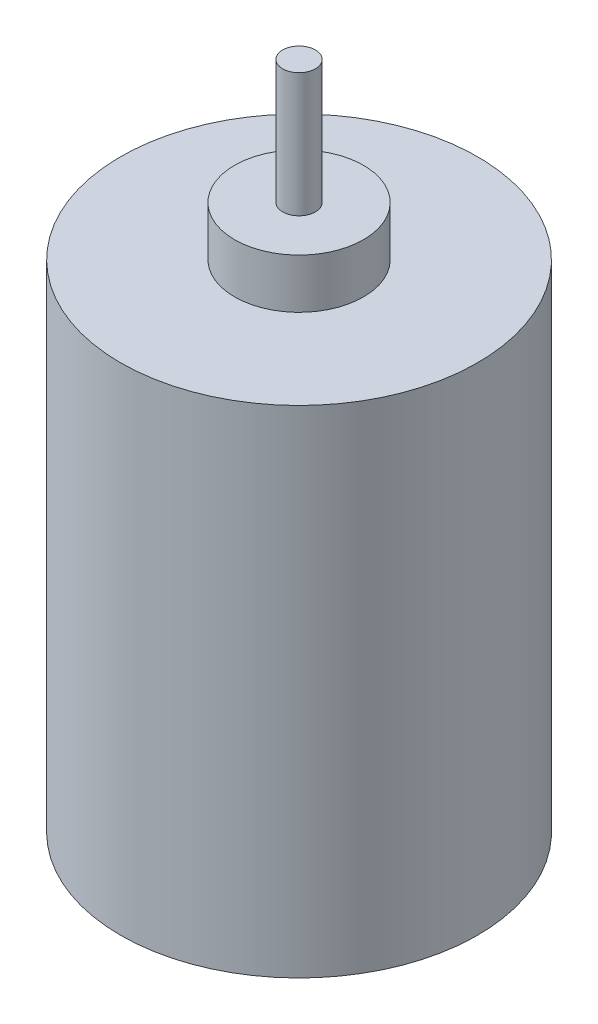
SolidWorks part; units mm, degrees
ref_plane "Front Plane" through (0, 0, 0) normal (0, 0, 1) x (1, 0, 0)
ref_plane "Top Plane" through (0, 0, 0) normal (0, 1, 0) x (1, 0, 0)
ref_plane "Right Plane" through (0, 0, 0) normal (1, 0, 0) x (0, 0, -1)
sketch "Sketch1" plane through (0, 0, 0) normal (0, 1, 0) x (1, 0, 0)
  circle A0 centre (0, 0) radius 18
  dimension "D1" = 36
extrude "Boss-Extrude1" add sketch "Sketch1" along normal blind 50
sketch "Sketch2" plane through (0, 0, 0) normal (0, 1, 0) x (1, 0, 0)
  circle A0 centre (0, 0) radius 6.5
  dimension "D1" = 13
extrude "Boss-Extrude2" add sketch "Sketch2" along normal blind 5 from surface starting at face at (0, 50, 18)
sketch "Sketch3" plane through (0, 0, 0) normal (0, 1, 0) x (1, 0, 0)
  circle A0 centre (0, 0) radius 1.65
  dimension "D1" = 3.3
extrude "Boss-Extrude3" add sketch "Sketch3" along normal blind 12.5 from surface starting at face at (0, 55, 6.5)
